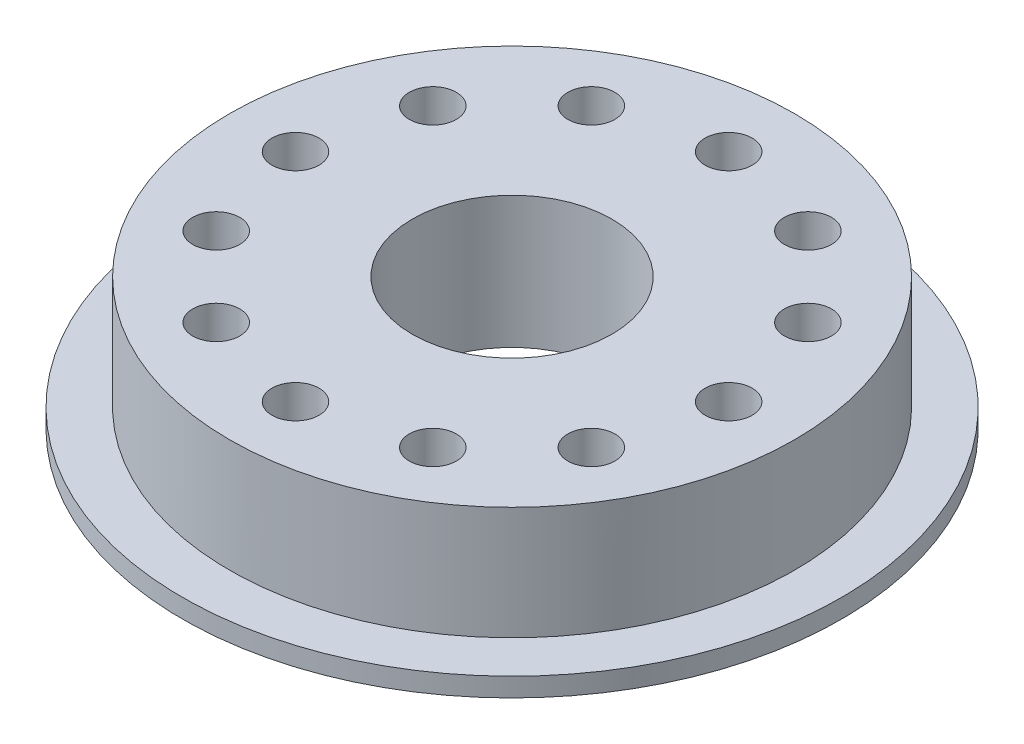
SolidWorks part; units mm, degrees
ref_plane "Front Plane" through (0, 0, 0) normal (0, 0, 1) x (1, 0, 0)
ref_plane "Top Plane" through (0, 0, 0) normal (0, 1, 0) x (1, 0, 0)
ref_plane "Right Plane" through (0, 0, 0) normal (1, 0, 0) x (0, 0, -1)
sketch "Sketch1" plane through (0, 0, 0) normal (0, 1, 0) x (1, 0, 0)
  circle A0 centre (0, 0) radius 30
  circle A1 centre (0, 0) radius 23 construction
  circle A8 centre (0, 0) radius 10.6
  point P18 (0, 0)
  dimension "D1" = 46
  dimension "D4" = 60
  dimension "D5" = 21.2
extrude "Boss-Extrude1" add sketch "Sketch1" along normal blind 14
sketch "Sketch2" plane through (0, 0, 0) normal (0, -1, 0) x (1, 0, 0)
  circle A0 centre (0, 0) radius 35
  dimension "D1" = 70
extrude "Boss-Extrude2" add sketch "Sketch2" against normal blind 2
sketch "Sketch3" plane through (0, 14, 0) normal (0, 1, 0) x (1, 0, 0)
  circle A0 centre (0, 0) radius 10.6
  circle A1 centre (0, 0) radius 23 construction
  circle A2 centre (0, 23) radius 2.5
  circle A3 centre (11.5, 19.9186) radius 2.5
  circle A4 centre (19.9186, 11.5) radius 2.5
  circle A5 centre (23, 0) radius 2.5
  circle A6 centre (19.9186, -11.5) radius 2.5
  circle A7 centre (11.5, -19.9186) radius 2.5
  circle A8 centre (0, -23) radius 2.5
  circle A9 centre (-11.5, -19.9186) radius 2.5
  circle A10 centre (-19.9186, -11.5) radius 2.5
  circle A11 centre (-23, 0) radius 2.5
  circle A12 centre (-19.9186, 11.5) radius 2.5
  circle A13 centre (-11.5, 19.9186) radius 2.5
  point P30 (0, 0)
  dimension "D1" = 46
  dimension "D2" = 5
extrude "Cut-Extrude1" cut sketch "Sketch3" against normal blind 64
